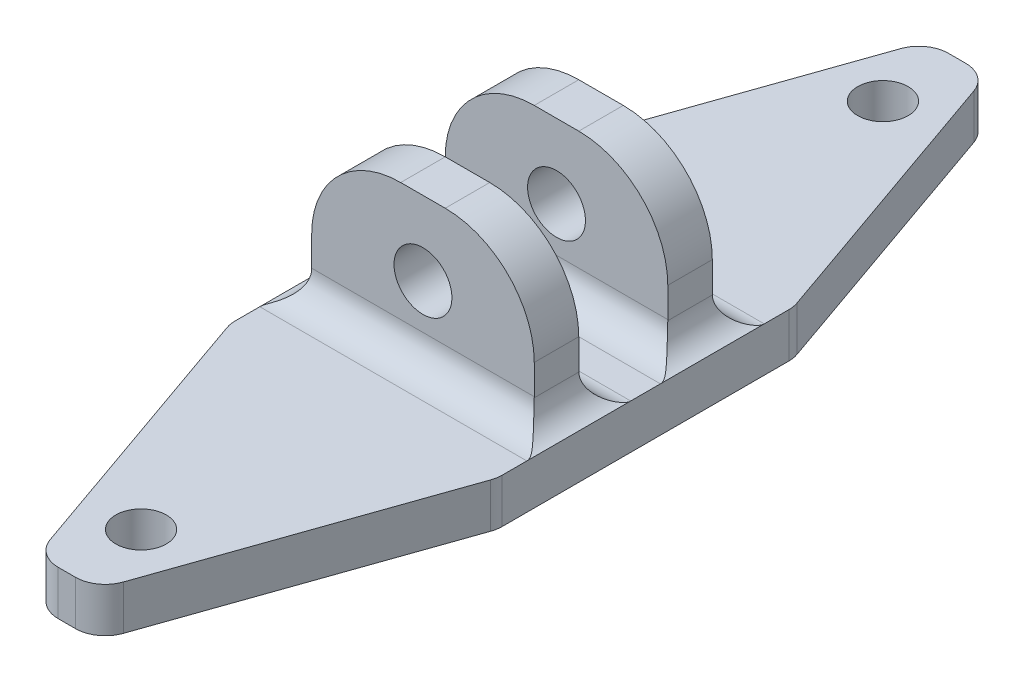
SolidWorks part; units mm, degrees
ref_plane "Front" through (0, 0, 0) normal (0, 0, 1) x (1, 0, 0)
ref_plane "Top" through (0, 0, 0) normal (0, 1, 0) x (1, 0, 0)
ref_plane "Right" through (0, 0, 0) normal (1, 0, 0) x (0, 0, -1)
sketch "草图1" plane through (0, 0, 0) normal (0, 1, 0) x (1, 0, 0)
  line L0 (2, 30) -> (9, 10)
  line L5 (9, -10) -> (2, -30)
  line L6 (9, -30) -> (-9, -30)
  line L7 (9, -30) -> (9, 30)
  line L8 (9, 30) -> (-9, 30)
  line L9 (-9, -30) -> (-9, 30)
  line L10 (-2, -30) -> (-9, -10)
  line L11 (-9, 10) -> (-2, 30)
  point P0 (0, 0)
  point P14 (0, 0)
  point P30 (0, 30)
  point P31 (-9, 0)
  dimension "D1" = 60
  dimension "D2" = 18
  dimension "D3" = 20
  dimension "D4" = 20
  dimension "D5" = 20
  dimension "D6" = 20
  dimension "D7" = 7
  dimension "D8" = 7
  dimension "D9" = 7
  dimension "D10" = 7
extrude "凸台-拉伸1" add sketch "草图1" against normal blind 3 contours L11 L9 L10 L6 L5 L7 L0 L8 region at (0, 0, 0)
sketch "草图2" plane through (0, 0, 0) normal (0, 1, 0) x (1, 0, 0)
  line L6 (0, 3) -> (0, -3) construction
  line L11 (-7.5, 6) -> (7.5, 6)
  line L12 (-7.5, 6) -> (-7.5, 3)
  line L13 (-7.5, 3) -> (7.5, 3)
  line L14 (7.5, 6) -> (7.5, 3)
  line L15 (-7.5, -3) -> (7.5, -3)
  line L16 (-7.5, -3) -> (-7.5, -6)
  line L17 (-7.5, -6) -> (7.5, -6)
  line L18 (7.5, -3) -> (7.5, -6)
  point P10 (0, 0)
  dimension "D1" = 6
  dimension "D2" = 3
  dimension "D3" = 3
  dimension "D4" = 15
extrude "凸台-拉伸2" add sketch "草图2" along normal blind 10
fillet "圆角1" radius 6 4 edges at (-7.5, 10, -4.5) (7.5, 10, -4.5) (7.5, 10, 4.5) (-7.5, 10, 4.5)
fillet "圆角2" radius 2 16 edges at (7.5, 0, 4.5) (7.5, 0, -4.5) (-7.5, 0, -4.5) (-7.5, 0, 4.5) (0, 0, 6) (0, 0, -6) (0, 0, 3) (0, 0, -3) (-9, -1.5, -10) (-9, -1.5, 10) (-2, -1.5, 30) (2, -1.5, 30) (9, -1.5, 10) (9, -1.5, -10) (2, -1.5, -30) (-2, -1.5, -30)
hole_wizard "M3 间隙孔1" positions "草图4" profile "草图5" hole size "M3" standard "GB" end condition through all
sketch "草图4" plane through (0, 0, 0) normal (0, 1, 0) x (1, 0, 0)
  line L0 (0, 25) -> (0, -25) construction
  point P0 (0, 25)
  point P2 (0, -25)
  point P11 (0, 0)
  dimension "D1" = 50
sketch "草图5" plane through (0, 0, -25) normal (1, 0, 0) x (0, 0, 1)
  line L0 (0, 0) -> (0, 3)
  line L1 (0, 3) -> (1.7, 3)
  line L2 (1.7, 3) -> (1.7, 0)
  line L5 (1.7, 0) -> (0, 0)
  line L11 (0, -6.35) -> (0, 107.95) construction
  dimension "通孔孔直径" = 3.4
  dimension "通孔孔深度" = 3
hole_wizard "M3.5 间隙孔1" positions "草图6" profile "草图7" hole size "M3.5" standard "GB" end condition through all
sketch "草图6" plane through (0, 0, -6) normal (0, 0, -1) x (-1, 0, 0)
  line L0 (0, 5) -> (0, 0) construction
  point P0 (0, 5)
  dimension "D1" = 5
sketch "草图7" plane through (0, 5, -6) normal (1, 0, 0) x (0, 1, 0)
  line L0 (0, 0) -> (0, 36)
  line L1 (0, 36) -> (1.95, 36)
  line L2 (1.95, 36) -> (1.95, 0)
  line L5 (1.95, 0) -> (0, 0)
  line L11 (0, -6.35) -> (0, 107.95) construction
  dimension "通孔孔直径" = 3.9
  dimension "通孔孔深度" = 36
equation "\"D10@草图1\"=\"D8@草图1\""
equation "\"D9@草图1\"=\"D8@草图1\""
equation "\"D7@草图1\"=\"D8@草图1\""
equation "\"D4@草图1\"=\"D3@草图1\""
equation "\"D6@草图1\"=\"D3@草图1\""
equation "\"D5@草图1\"=\"D3@草图1\""
